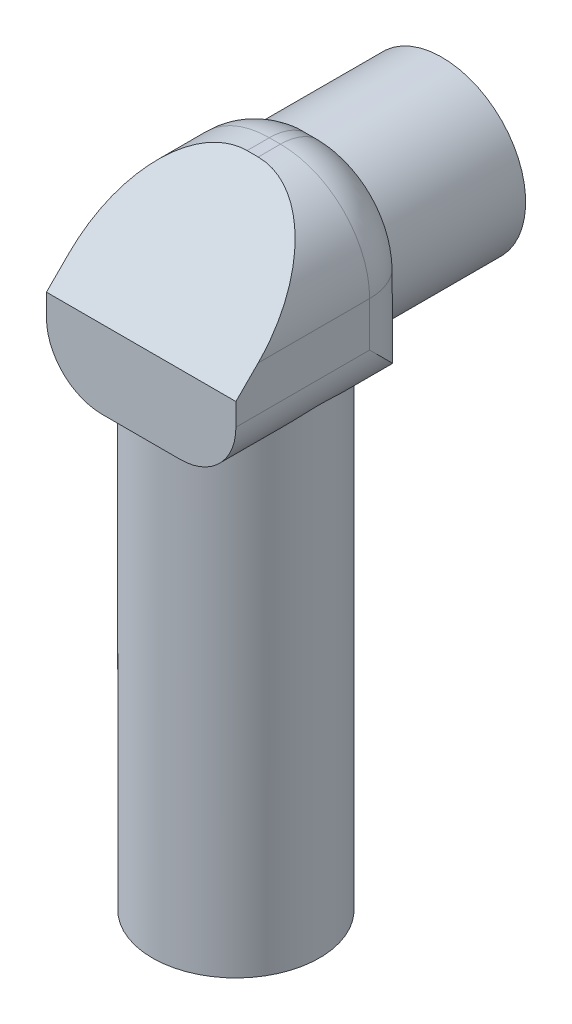
SolidWorks part; units mm, degrees
ref_plane "Front Plane" through (0, 0, 0) normal (0, 0, 1) x (1, 0, 0)
ref_plane "Top Plane" through (0, 0, 0) normal (0, 1, 0) x (1, 0, 0)
ref_plane "Right Plane" through (0, 0, 0) normal (1, 0, 0) x (0, 0, -1)
sketch "Sketch1" plane through (0, 0, 0) normal (0, 1, 0) x (1, 0, 0)
  circle A0 centre (0, 0) radius 7.5
  circle A1 centre (0, 0) radius 2.4
  dimension "D1" = 4.8
  dimension "D2" = 15
extrude "Boss-Extrude1" add sketch "Sketch1" along normal blind 58
sketch "Sketch2" plane through (0, 58, 0) normal (0, 1, 0) x (1, 0, 0)
  line L1 (-8.5, 8.5) -> (8.5, 8.5)
  line L2 (-8.5, 8.5) -> (-8.5, -8.5)
  line L3 (-8.5, -8.5) -> (8.5, -8.5)
  line L4 (8.5, 8.5) -> (8.5, -8.5)
  line L5 (-8.5, 8.5) -> (8.5, -8.5) construction
  line L6 (-8.5, -8.5) -> (8.5, 8.5) construction
  point P0 (0, 0)
  dimension "D1" = 17
extrude "Boss-Extrude2" add sketch "Sketch2" against normal blind 17
sketch "Sketch3" plane through (0, 0, -8.5) normal (0, 0, -1) x (-1, 0, 0)
  line L3 (8.5, 58) -> (-8.5, 41) construction
  circle A0 centre (0, 49.5) radius 7.5
  circle A1 centre (0, 49.5) radius 2.4
  point P4 (0, 37.5)
  dimension "D1" = 4.8
  dimension "D2" = 15
extrude "Boss-Extrude3" add sketch "Sketch3" along normal blind 10
fillet "Fillet5" radius 8 2 edges at (-8.5, 58, 0) (8.5, 58, 0)
chamfer "Chamfer1" distance 10 angle 45 3 edges at (0, 58, 8.5) (6.1569, 55.6569, 8.5) (-6.1569, 55.6569, 8.5)
fillet "Fillet4" radius 5 4 edges at (-8.5, 45.5, -8.5) (8.5, 45.5, -8.5) (8.5, 41, 0) (-8.5, 41, 0)
